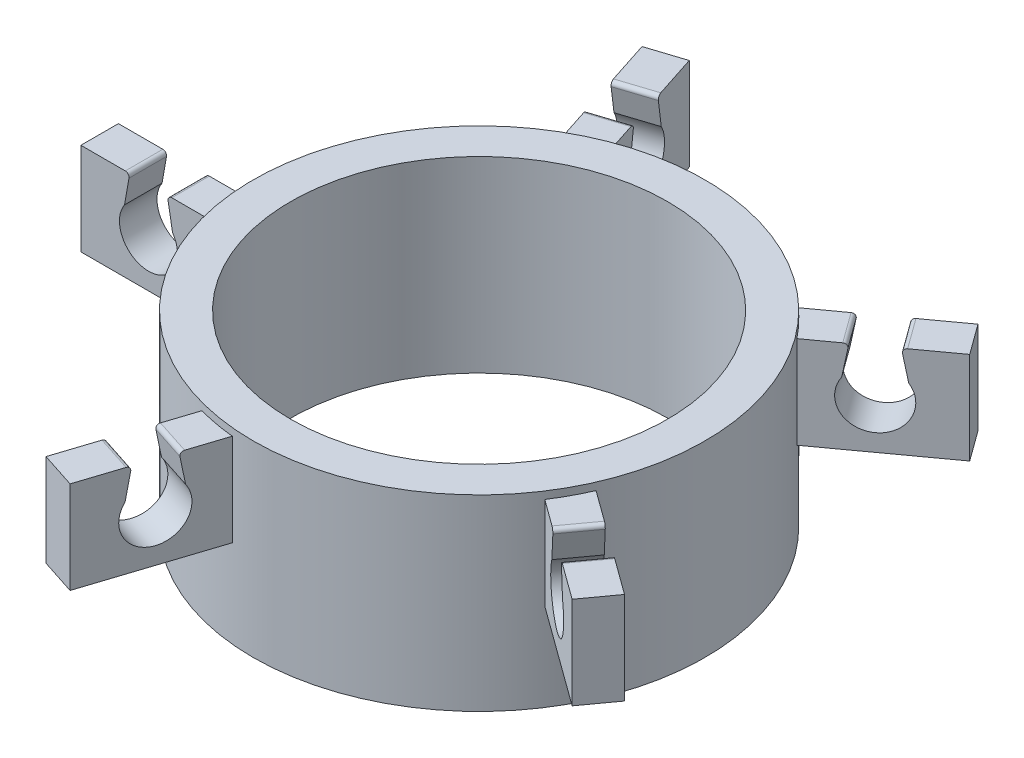
SolidWorks part; units mm, degrees
ref_plane "Plan de face" through (0, 0, 0) normal (0, 0, 1) x (1, 0, 0)
ref_plane "Plan de dessus" through (0, 0, 0) normal (0, 1, 0) x (1, 0, 0)
ref_plane "Plan de droite" through (0, 0, 0) normal (1, 0, 0) x (0, 0, -1)
sketch "Esquisse1" plane through (0, 0, 0) normal (0, 1, 0) x (1, 0, 0)
  circle A0 centre (0, 0) radius 10.05
  circle A1 centre (0, 0) radius 12.05
  dimension "D1" = 20.1
  dimension "D2" = 2
extrude "BASE" add sketch "Esquisse1" along normal blind 10
ref_axis "AXE BAGUE" through (0, 10, 0) along (0, -1, 0)
ref_plane "PLAN TUGE ASS" through (0, 0, 2.6) normal (0, 0, -1) x (-1, 0, 0)
sketch "Esquisse7" plane through (0, 0, 2.6) normal (0, 0, -1) x (-1, 0, 0)
  line L0 (15.0226, 7.1469) -> (15.0226, 9.9507) construction
  line L1 (11.4157, 9.6084) -> (18.6295, 9.6084)
  line L2 (11.4157, 9.6084) -> (11.4157, 4.6854)
  line L3 (11.4157, 4.6854) -> (18.6295, 4.6854)
  line L4 (18.6295, 9.6084) -> (18.6295, 4.6854)
  line L5 (11.4157, 9.6084) -> (18.6295, 4.6854) construction
  line L6 (11.4157, 4.6854) -> (18.6295, 9.6084) construction
  line L7 (16.3029, 8.0206) -> (16.0226, 9.6084)
  line L8 (13.7424, 8.0206) -> (14.0226, 9.6084)
  arc A2 (13.7424, 8.0206) -> (16.3029, 8.0206) centre (15.0226, 7.1469) ccw
  dimension "D1" = 3.1
  dimension "D2" = 4.923
  dimension "D3" = 1
  dimension "D4" = 1
extrude "BOSS TIGE" add sketch "Esquisse7" along normal blind 2 contours A2 L8 L1 L2 L3 L4 L7 region at (-12.7192, 9.5211, 2.6)
fillet "CONGE TIGE" radius 0.2 2 edges at (-16.0226, 9.6084, 1.6) (-14.0226, 9.6084, 1.6)
pattern_circular "REP SUPPORT TIGE" count 5 over 360 about axis through (0, 10, 0) along (0, -1, 0) of "CONGE TIGE", "BOSS TIGE"
